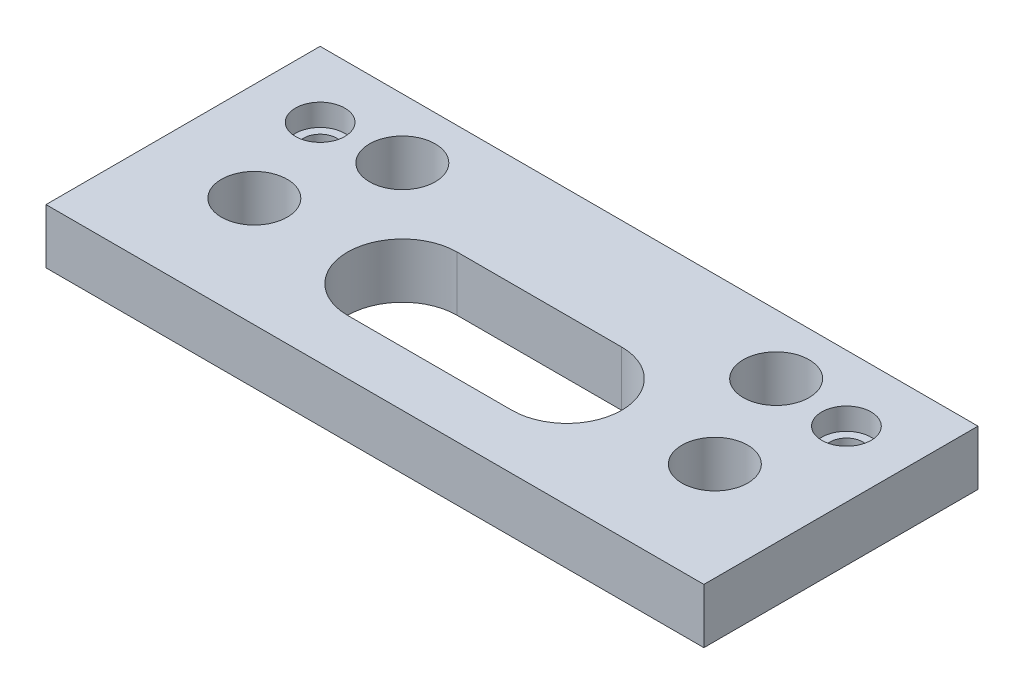
SolidWorks part; units mm, degrees
ref_plane "Front Plane" through (0, 0, 0) normal (0, 0, 1) x (1, 0, 0)
ref_plane "Top Plane" through (0, 0, 0) normal (0, 1, 0) x (1, 0, 0)
ref_plane "Right Plane" through (0, 0, 0) normal (1, 0, 0) x (0, 0, -1)
sketch "Sketch1" plane through (0, 0, 0) normal (0, 1, 0) x (1, 0, 0)
  line L0 (54, 19) -> (54, 25) construction
  line L1 (0, 0) -> (60, 0)
  line L2 (0, 0) -> (0, 25)
  line L3 (0, 25) -> (60, 25)
  line L4 (60, 0) -> (60, 25)
  line L5 (6, 19) -> (6, 25) construction
  line L6 (6, 19) -> (0, 19) construction
  line L7 (54, 19) -> (60, 19) construction
  circle A0 centre (6, 19) radius 1.5
  circle A1 centre (54, 19) radius 1.5
  dimension "D3" = 3
  dimension "D1" = 6
  dimension "D2" = 6
  dimension "D4" = 25
  dimension "D5" = 60
extrude "body" add sketch "Sketch1" along normal blind 5 contours L2 L3 L4 L1 | A0 | A1
sketch "Sketch2" plane through (0, 5, 0) normal (0, 1, 0) x (1, 0, 0)
  circle A0 centre (6, 19) radius 2.25
  circle A1 centre (54, 19) radius 2.25
  dimension "D1" = 4.5
extrude "screwHoles" cut sketch "Sketch2" against normal blind 2
sketch "Sketch3" plane through (0, 5, 0) normal (0, 1, 0) x (1, 0, 0)
  line L0 (30, 0) -> (30, 25) construction
  line L1 (0, 0) -> (60, 0) construction
  line L2 (0, 25) -> (60, 25) construction
  line L3 (22.5, 10) -> (37.5, 10) construction
  line L4 (22.5, 10) -> (37.5, 10) construction
  line L5 (22.5, 15) -> (37.5, 15)
  line L6 (22.5, 5) -> (37.5, 5)
  line L7 (9, 10) -> (22.5, 10) construction
  line L8 (37.5, 10) -> (51, 10) construction
  line L9 (22.5, 10) -> (18.9645, 13.5355) construction
  line L10 (18.9645, 13.5355) -> (7.5, 25) construction
  line L11 (37.5, 10) -> (41.0355, 13.5355) construction
  line L12 (6, 10) -> (0, 10) construction
  line L13 (41.0355, 13.5355) -> (52.5, 25) construction
  line L14 (0, 0) -> (0, 25) construction
  line L15 (54, 10) -> (60, 10) construction
  line L16 (60, 0) -> (60, 25) construction
  line L17 (12.9541, 19.5459) -> (47.0459, 19.5459) construction
  arc A0 (22.5, 15) -> (22.5, 5) centre (22.5, 10) ccw
  arc A1 (37.5, 5) -> (37.5, 15) centre (37.5, 10) ccw
  circle A2 centre (9, 10) radius 3
  circle A3 centre (51, 10) radius 3
  arc A4 (9, 10) -> (12.9541, 19.5459) centre (22.5, 10) cw construction
  circle A5 centre (12.9541, 19.5459) radius 3
  circle A6 centre (47.0459, 19.5459) radius 3
  point P8 (30, 10)
  point P9 (30, 10)
  dimension "D2" = 5
  dimension "D5" = 6
  dimension "D1" = 15
  dimension "D3" = 5
  dimension "D4" = 6
  dimension "D6" = 45
extrude "buttonHoles" cut sketch "Sketch3" against normal up to next
